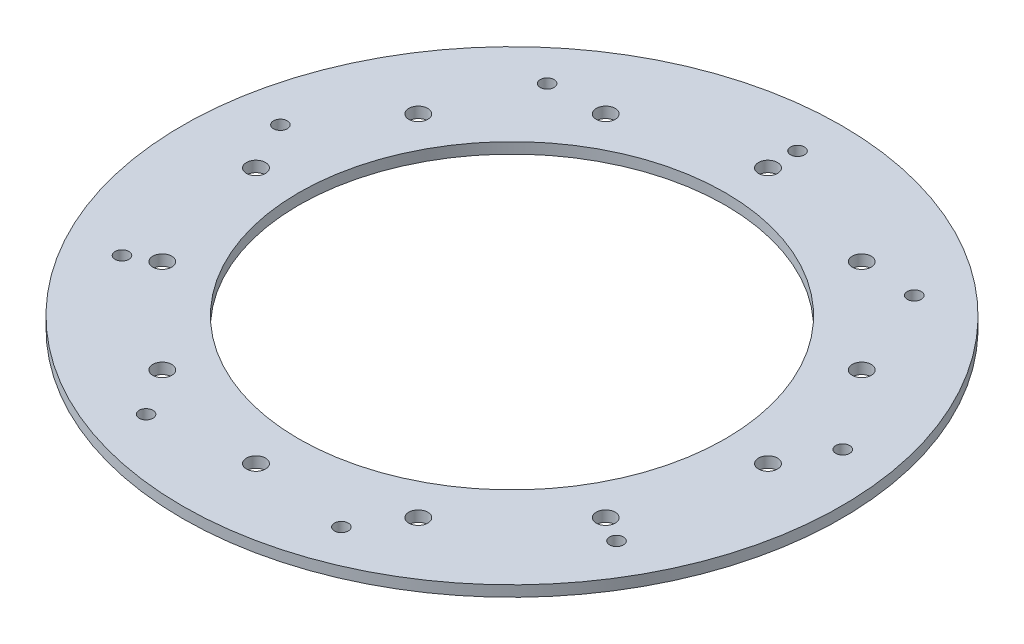
SolidWorks part; units mm, degrees
material "1060 Alloy"
ref_plane "Ebene vorne" through (0, 0, 0) normal (0, 0, 1) x (1, 0, 0)
ref_plane "Ebene oben" through (0, 0, 0) normal (0, 1, 0) x (1, 0, 0)
ref_plane "Ebene rechts" through (0, 0, 0) normal (1, 0, 0) x (0, 0, -1)
sketch "Sketch1" plane through (0, 0, 0) normal (0, 1, 0) x (1, 0, 0)
  circle A0 centre (0, 0) radius 49.3
  circle A1 centre (0, 0) radius 76.182
  dimension "D1" = 152.364
  dimension "D2" = 98.6
extrude "Boss-Extrude1" add sketch "Sketch1" along normal blind 2.5
sketch "Sketch2" plane through (0, 2.5, 0) normal (0, 1, 0) x (1, 0, 0)
  circle A0 centre (0, 66) radius 1.6
  point P21 (0, 4)
  point P28 (0, 0)
  dimension "D1" = 3.2
  dimension "D2" = 66
extrude "Cut-Extrude1" cut sketch "Sketch2" against normal through all
sketch "Sketch3" plane through (0, 2.5, 0) normal (0, 1, 0) x (1, 0, 0)
  circle A0 centre (0, 59.18) radius 2.2
  circle A1 centre (29.59, 51.2514) radius 2.2
  circle A2 centre (51.2514, 29.59) radius 2.2
  circle A3 centre (59.18, 0) radius 2.2
  circle A4 centre (51.2514, -29.59) radius 2.2
  circle A5 centre (29.59, -51.2514) radius 2.2
  circle A6 centre (0, -59.18) radius 2.2
  circle A7 centre (-29.59, -51.2514) radius 2.2
  circle A8 centre (-51.2514, -29.59) radius 2.2
  circle A9 centre (-59.18, 0) radius 2.2
  circle A10 centre (-51.2514, 29.59) radius 2.2
  circle A11 centre (-29.59, 51.2514) radius 2.2
  point P28 (0, 0)
  dimension "D1" = 4.4
  dimension "D3" = 118.36
  dimension "D2" = 12
extrude "Cut-Extrude2" cut sketch "Sketch3" against normal through all
pattern_circular "CirPattern1" count 9 over 360 about axis through (0, 2.5, 0) along (0, -1, 0) of "Cut-Extrude1"
equation "\"d_i_tube\"= 150mm'Inner Rocket Body Composite Tube Diameter"
equation "\"t_tube\"= 1.182mm'Thickness of Rocket Body Composite Tube"
equation "\"l_upper_body_tube\"= 1190mm'Upper Rocket Body Composite Tube length"
equation "\"l_lower_body_tube\"= 896mm'Lower Rocket Body Composite Tube Length"
equation "\"d_a_NC\"= 154mm'Outer Diameter of Nosecone base"
equation "\"d_i_phenolic_tube\"= 152.3mm'Inner Phenolic Tube Diameter"
equation "\"t_phenolic_tube\"= 2mm'Thickness of Phenolic Body Tube"
equation "\"l_fin_cut\"= 220mm'Length of fin on Motor Retainer"
equation "\"t_SW-Panel\"= 11.482mm'Thickness of Sandwich-Panel"
equation "\"l_motor_tube\"=650mm'Length of phenolic motor tube"
equation "\"d_i_motor_tube\"=99.06mm'Inner diameter of phenolic motor tube"
equation "\"t_motor_tube\"=1.58mm'Thicknes of phenolic motor tube"
equation "\"l_cut_fin_centering\"=13mm'Length of cut for fin alignement on fin centering rings"
equation "\"D1@Sketch1\"=\"d_i_tube\"+\"t_tube\"*2"
